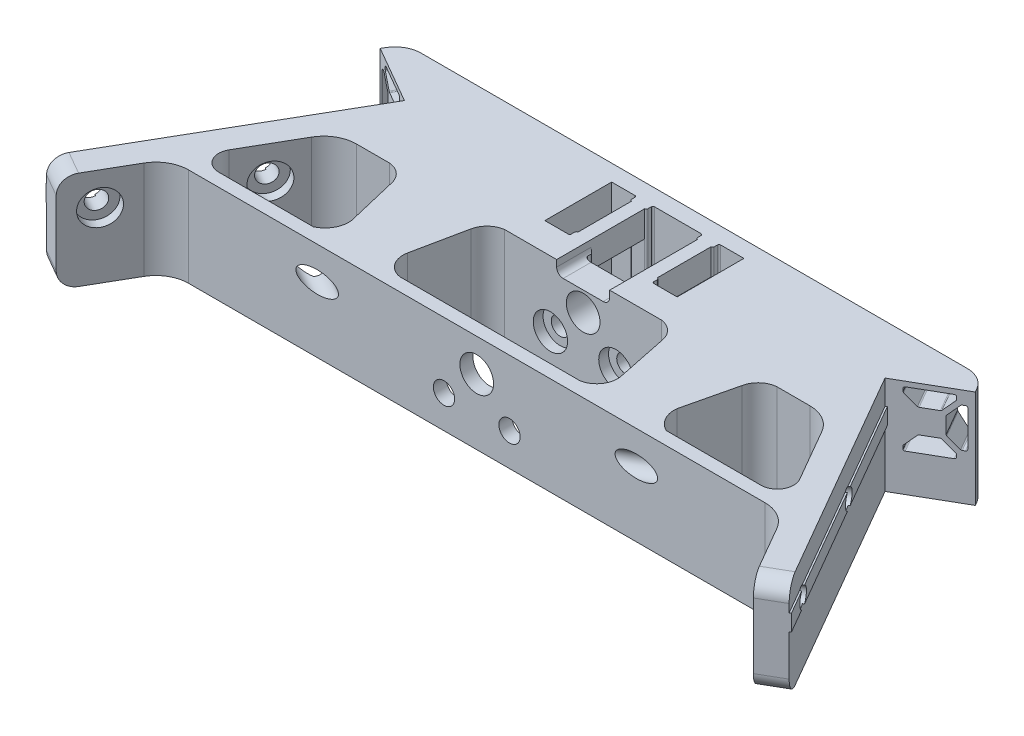
SolidWorks part; units mm, degrees
ref_plane "Front Plane" through (0, 0, 0) normal (0, 0, 1) x (1, 0, 0)
ref_plane "Top Plane" through (0, 0, 0) normal (0, 1, 0) x (1, 0, 0)
ref_plane "Right Plane" through (0, 0, 0) normal (1, 0, 0) x (0, 0, -1)
sketch "Sketch1" plane through (0, 0, 0) normal (0, 1, 0) x (1, 0, 0)
  line L0 (0, -61.4) -> (0, -111.1933) construction
  line L1 (0, 0) -> (-7.6, 0) construction
  line L2 (0, 0) -> (0, -20.4) construction
  line L3 (0, -20.4) -> (-7.1, -20.4) construction
  line L4 (-20.2, 0) -> (-20.2, -20.4)
  line L5 (0, 5) -> (-83.3812, 5)
  line L6 (-90.3094, 1) -> (-90.8868, 0)
  line L7 (-90.8868, 0) -> (-73.393, -10.1)
  line L8 (-73.393, -10.1) -> (-113.393, -79.382)
  line L9 (-113.393, -79.382) -> (-106.4648, -83.382)
  line L10 (-106.4648, -83.382) -> (-96.6603, -66.4)
  line L11 (-69.2361, -28.9) -> (0, -28.9)
  line L12 (0, -57.4) -> (0, -61.4)
  line L13 (0, -20.4) -> (-7.1, -20.4)
  line L14 (-20.2, 0) -> (-13.1, 0)
  line L16 (-82.8038, -57.4) -> (0, -57.4)
  line L17 (0, -20.4) -> (0, -28.9)
  line L18 (0, -61.4) -> (-88, -61.4)
  line L19 (-87.134, -49.9) -> (-77.8964, -33.9)
  line L20 (0, 0) -> (0, -20.4) construction
  line L21 (-7.6, -0.5) -> (-7.6, -1.5)
  line L22 (-20.2, -10.2) -> (0, -10.2) construction
  line L23 (-8.1, -2) -> (-12.1, -2)
  line L24 (-12.6, -0.5) -> (-12.6, -1.5)
  line L25 (-12.6, -19.9) -> (-12.6, -18.9)
  line L26 (-8.1, -18.4) -> (-12.1, -18.4)
  line L28 (-7.1, 0) -> (0, 0)
  line L29 (-7.6, -19.9) -> (-7.6, -18.9)
  line L30 (-13.1, -20.4) -> (-20.2, -20.4) construction
  line L31 (-13.1, -20.4) -> (-20.2, -20.4)
  line L32 (0, -28.9) -> (0, -57.4) construction
  line L33 (0, 5) -> (0, 0)
  arc A0 (-88, -61.4) -> (-96.6603, -66.4) centre (-88, -71.4) ccw
  arc A1 (-77.8964, -33.9) -> (-69.2361, -28.9) centre (-69.2361, -38.9) cw
  arc A2 (-82.8038, -57.4) -> (-87.134, -49.9) centre (-82.8038, -52.4) cw
  arc A3 (-83.3812, 5) -> (-90.3094, 1) centre (-83.3812, -3) ccw
  arc A4 (-7.1, 0) -> (-7.6, -0.5) centre (-7.1, -0.5) ccw
  arc A5 (-12.6, -0.5) -> (-13.1, 0) centre (-13.1, -0.5) ccw
  arc A6 (-7.6, -1.5) -> (-8.1, -2) centre (-8.1, -1.5) cw
  arc A7 (-12.1, -2) -> (-12.6, -1.5) centre (-12.1, -1.5) cw
  arc A10 (-12.1, -18.4) -> (-12.6, -18.9) centre (-12.1, -18.9) ccw
  arc A11 (-7.6, -18.9) -> (-8.1, -18.4) centre (-8.1, -18.9) ccw
  arc A12 (-12.6, -19.9) -> (-13.1, -20.4) centre (-13.1, -19.9) cw
  arc A13 (-7.1, -20.4) -> (-7.6, -19.9) centre (-7.1, -19.9) cw
  point P24 (-91.4641, -57.4)
  point P27 (-88, 5)
  point P30 (-10.1, 0)
  point P63 (-10.1, -20.4)
  dimension "D13" = 10
  dimension "D14" = 5
  dimension "D15" = 8
  dimension "D17" = 0.5
  dimension "D18" = 20.2
  dimension "D2" = 20.4
  dimension "D3" = 5
  dimension "D4" = 88
  dimension "D5" = 120
  dimension "D6" = 5
  dimension "D7" = 20.2
  dimension "D8" = 80
  dimension "D9" = 8
  dimension "D10" = 8.5
  dimension "D11" = 4
  dimension "D12" = 37
  dimension "D16" = 5
extrude "Boss-Extrude2" add sketch "Sketch1" along normal blind 30
sketch "Sketch2" plane through (-50.6714, 0, -29.2551) normal (-0.866, 0, -0.5) x (-0.5, 0, 0.866)
  line L0 (45.4434, 30) -> (45.4434, 0) construction
  line L1 (45.4434, 22.5) -> (125.4434, 22.5)
  line L2 (45.4434, 22.5) -> (45.4434, 17.5)
  line L3 (45.4434, 17.5) -> (125.4434, 17.5)
  line L4 (125.4434, 22.5) -> (125.4434, 17.5)
  line L5 (125.4434, 30) -> (125.4434, 0) construction
  line L7 (45.4434, 15) -> (125.4434, 15) construction
  line L9 (45.4434, 30) -> (125.4434, 30) construction
  dimension "D1" = 5
  dimension "D2" = 7.5
extrude "Boss-Extrude3" add sketch "Sketch2" along normal blind 0.5
hole_wizard "CBORE for M5 SHCS2" positions "Sketch5" profile "Sketch4" counterbore size "M5" standard "ANSI Metric" end condition up to next
sketch "Sketch5" plane through (-43.7431, 0, -25.2551) normal (0.866, 0, 0.5) x (0.5, 0, -0.866)
  line L0 (-125.4434, 20) -> (-68.3064, 20) construction
  line L1 (-125.4434, 30) -> (-125.4434, 0) construction
  line L2 (-68.3064, 30) -> (-68.3064, 0) construction
  line L4 (-86.7817, 30) -> (-68.3064, 30) construction
  line L10 (-125.4434, 30) -> (-105.8342, 30) construction
  line L11 (-115.6388, 30) -> (-115.6388, 20) construction
  line L13 (-77.5441, 30) -> (-77.5441, 20) construction
  point P0 (-77.5441, 20)
  point P4 (-115.6388, 20)
  dimension "D1" = 10
sketch "Sketch4" plane through (-82.5152, 20, 41.9) normal (0, 1, 0) x (0.5, 0, -0.866)
  line L0 (0, 0) -> (0, 8.5)
  line L1 (0, 8.5) -> (2.75, 8.5)
  line L3 (2.75, 8.5) -> (2.75, 3)
  line L4 (2.75, 3) -> (5.25, 3)
  line L5 (5.25, 3) -> (5.25, 0)
  line L7 (5.25, 0) -> (0, 0)
  line L11 (0, -6.35) -> (0, 107.95) construction
  dimension "Thru Hole Dia." = 5.5
  dimension "Thru Hole Depth" = 8.5
  dimension "C'Bore Dia." = 10.5
  dimension "C'Bore Depth" = 3
hole_wizard "CBORE for M5 SHCS3" positions "Sketch7" profile "Sketch6" counterbore size "M5" standard "ANSI Metric" end condition up to next
sketch "Sketch7" plane through (0, 0, 28.9) normal (0, 0, 1) x (1, 0, 0)
  line L0 (0, 60) -> (0, 0) construction
  line L2 (-69.2361, 0) -> (0, 0) construction
  line L4 (0, 10) -> (-28.3411, 10)
  line L10 (0, 30) -> (0, 0) construction
  line L11 (-69.2361, 0) -> (0, 0) construction
  point P2 (-10, 10)
  dimension "D1" = 10
  dimension "D2" = 10
sketch "Sketch6" plane through (-10, 10, 28.9) normal (1, 0, 0) x (0, -1, 0)
  line L0 (0, 0) -> (0, 10.5)
  line L1 (0, 10.5) -> (2.75, 10.5)
  line L3 (2.75, 10.5) -> (2.75, 3)
  line L4 (2.75, 3) -> (5.25, 3)
  line L5 (5.25, 3) -> (5.25, 0)
  line L7 (5.25, 0) -> (0, 0)
  line L11 (0, -6.35) -> (0, 107.95) construction
  dimension "Thru Hole Dia." = 5.5
  dimension "Thru Hole Depth" = 10.5
  dimension "C'Bore Dia." = 10.5
  dimension "C'Bore Depth" = 3
fillet "Fillet1" radius 5 2 edges at (-109.9289, 0, 81.382) (-109.9289, 30, 81.382)
sketch "Sketch17" plane through (0, 0, 0) normal (0, 1, 0) x (1, 0, 0)
  line L0 (-77.8964, -33.9) -> (-8.392, -33.9) construction
  line L1 (0, -57.4) -> (-82.8038, -57.4) construction
  line L2 (-87.134, -49.9) -> (-8.392, -49.9) construction
  line L3 (-49.7313, -49.9) -> (-53.5337, -33.9)
  line L4 (-69.2361, -28.9) -> (0, -28.9) construction
  line L5 (-29.3026, -33.9) -> (-32.6088, -49.9)
  line L6 (-59.1642, -28.9) -> (-23.9792, -28.9)
  line L7 (-69.2361, -28.9) -> (0, -28.9) construction
  line L8 (-27.5009, -57.4) -> (-53.9252, -57.4)
  arc A0 (-29.3026, -33.9) -> (-23.9792, -28.9) centre (-23.0863, -35.1845) cw
  arc A1 (-32.6088, -49.9) -> (-27.5009, -57.4) centre (-26.4248, -51.1778) ccw
  arc A2 (-53.5337, -33.9) -> (-59.1642, -28.9) centre (-59.7018, -35.1756) ccw
  arc A3 (-49.7313, -49.9) -> (-53.9252, -57.4) centre (-56.9594, -50.7807) cw
  point P22 (-53.9252, -57.4)
  point P25 (-60.4891, -28.9)
  point P26 (-60.4891, -28.9)
  point P29 (-25.9078, -57.4)
  point P32 (-22.3891, -28.9)
extrude "Boss-Extrude5" add sketch "Sketch17" along normal up to surface (30 mm away) up to face at (-35.0167, 30, 22.2446)
sketch "Sketch21" plane through (-22.7217, 0, 39.3551) normal (-0.5, 0, 0.866) x (0.866, 0, 0.5)
  line L0 (-70.8942, 16.345) -> (-66.1263, 16.345)
  line L1 (-65.7671, 16.1962) -> (-62.664, 13.0931)
  line L2 (-62.5152, 12.7339) -> (-62.5152, 12.008)
  line L3 (-63.0232, 11.5) -> (-73.9972, 11.5)
  line L4 (-70.8147, 17.8751) -> (-70.6351, 17.6955)
  line L5 (-66.3853, 17.6955) -> (-66.2057, 17.8751)
  line L6 (-66.2057, 22.1249) -> (-66.3853, 22.3045)
  line L7 (-70.6351, 22.3045) -> (-70.8147, 22.1249)
  line L8 (-70.8147, 17.8751) -> (-70.6351, 17.6955) construction
  line L9 (-66.3853, 17.6955) -> (-66.2057, 17.8751) construction
  line L10 (-66.2057, 22.1249) -> (-66.3853, 22.3045) construction
  line L11 (-70.6351, 22.3045) -> (-70.8147, 22.1249) construction
  line L12 (-74.5052, 12.008) -> (-74.5052, 12.7339)
  line L13 (-74.3564, 13.0931) -> (-71.2534, 16.1962)
  line L14 (-72.1652, 22.3839) -> (-72.1652, 17.6161)
  line L15 (-72.314, 17.2569) -> (-75.4171, 14.1538)
  line L16 (-75.7763, 14.005) -> (-76.5022, 14.005)
  line L17 (-77.0102, 14.513) -> (-77.0102, 25.487)
  line L18 (-76.5022, 25.995) -> (-75.7763, 25.995)
  line L19 (-75.4171, 25.8462) -> (-72.314, 22.7431)
  line L20 (-73.9972, 28.5) -> (-63.0232, 28.5)
  line L21 (-62.5152, 27.992) -> (-62.5152, 27.2661)
  line L22 (-62.664, 26.9069) -> (-65.7671, 23.8038)
  line L23 (-66.1263, 23.655) -> (-70.8942, 23.655)
  line L24 (-71.2534, 23.8038) -> (-74.3564, 26.9069)
  line L25 (-74.5052, 27.2661) -> (-74.5052, 27.992)
  line L52 (-74.5052, 12.008) -> (-74.5052, 12.7339)
  line L53 (-71.6482, 11.5) -> (-73.9972, 11.5)
  line L54 (-71.1402, 10.508) -> (-71.1402, 10.992)
  line L55 (-77.0102, 10) -> (-71.6482, 10)
  line L56 (-78.5102, 16.862) -> (-78.5102, 11.5)
  line L57 (-77.5182, 17.37) -> (-78.0022, 17.37)
  line L58 (-77.0102, 14.513) -> (-77.0102, 16.862)
  line L59 (-75.7763, 14.005) -> (-76.5022, 14.005)
  line L60 (-72.314, 17.2569) -> (-75.4171, 14.1538)
  line L61 (-72.1652, 22.3839) -> (-72.1652, 17.6161)
  line L62 (-75.4171, 25.8462) -> (-72.314, 22.7431)
  line L63 (-76.5022, 25.995) -> (-75.7763, 25.995)
  line L64 (-77.0102, 23.138) -> (-77.0102, 25.487)
  line L65 (-78.0022, 22.63) -> (-77.5182, 22.63)
  line L66 (-78.5102, 28.5) -> (-78.5102, 23.138)
  line L67 (-71.6482, 30) -> (-77.0102, 30)
  line L68 (-71.1402, 29.008) -> (-71.1402, 29.492)
  line L69 (-73.9972, 28.5) -> (-71.6482, 28.5)
  line L70 (-74.5052, 27.2661) -> (-74.5052, 27.992)
  line L71 (-71.2534, 23.8038) -> (-74.3564, 26.9069)
  line L72 (-66.1263, 23.655) -> (-70.8942, 23.655)
  line L73 (-62.664, 26.9069) -> (-65.7671, 23.8038)
  line L74 (-62.5152, 27.992) -> (-62.5152, 27.2661)
  line L75 (-65.3722, 28.5) -> (-63.0232, 28.5)
  line L76 (-65.8802, 29.492) -> (-65.8802, 29.008)
  line L77 (-60.0102, 30) -> (-65.3722, 30)
  line L78 (-58.5102, 23.138) -> (-58.5102, 28.5)
  line L79 (-59.5022, 22.63) -> (-59.0182, 22.63)
  line L80 (-60.0102, 25.487) -> (-60.0102, 23.138)
  line L81 (-61.2442, 25.995) -> (-60.5182, 25.995)
  line L82 (-64.7064, 22.7431) -> (-61.6034, 25.8462)
  line L83 (-64.8552, 17.6161) -> (-64.8552, 22.3839)
  line L84 (-61.6034, 14.1538) -> (-64.7064, 17.2569)
  line L85 (-60.5182, 14.005) -> (-61.2442, 14.005)
  line L86 (-60.0102, 16.862) -> (-60.0102, 14.513)
  line L87 (-59.0182, 17.37) -> (-59.5022, 17.37)
  line L88 (-58.5102, 11.5) -> (-58.5102, 16.862)
  line L89 (-65.3722, 10) -> (-60.0102, 10)
  line L90 (-65.8802, 10.992) -> (-65.8802, 10.508)
  line L91 (-63.0232, 11.5) -> (-65.3722, 11.5)
  line L92 (-62.5152, 12.7339) -> (-62.5152, 12.008)
  line L93 (-65.7671, 16.1962) -> (-62.664, 13.0931)
  line L94 (-70.8942, 16.345) -> (-66.1263, 16.345)
  line L95 (-74.3564, 13.0931) -> (-71.2534, 16.1962)
  line L96 (-74.5052, 12.008) -> (-74.5052, 12.7339) construction
  line L97 (-71.6482, 11.5) -> (-73.9972, 11.5) construction
  line L98 (-71.1402, 10.508) -> (-71.1402, 10.992) construction
  line L99 (-77.0102, 10) -> (-71.6482, 10) construction
  line L100 (-78.5102, 16.862) -> (-78.5102, 11.5) construction
  line L101 (-77.5182, 17.37) -> (-78.0022, 17.37) construction
  line L102 (-77.0102, 14.513) -> (-77.0102, 16.862) construction
  line L103 (-75.7763, 14.005) -> (-76.5022, 14.005) construction
  line L104 (-72.314, 17.2569) -> (-75.4171, 14.1538) construction
  line L105 (-72.1652, 22.3839) -> (-72.1652, 17.6161) construction
  line L106 (-75.4171, 25.8462) -> (-72.314, 22.7431) construction
  line L107 (-76.5022, 25.995) -> (-75.7763, 25.995) construction
  line L108 (-77.0102, 23.138) -> (-77.0102, 25.487) construction
  line L109 (-78.0022, 22.63) -> (-77.5182, 22.63) construction
  line L110 (-78.5102, 28.5) -> (-78.5102, 23.138) construction
  line L111 (-71.6482, 30) -> (-77.0102, 30) construction
  line L112 (-71.1402, 29.008) -> (-71.1402, 29.492) construction
  line L113 (-73.9972, 28.5) -> (-71.6482, 28.5) construction
  line L114 (-74.5052, 27.2661) -> (-74.5052, 27.992) construction
  line L115 (-71.2534, 23.8038) -> (-74.3564, 26.9069) construction
  line L116 (-66.1263, 23.655) -> (-70.8942, 23.655) construction
  line L117 (-62.664, 26.9069) -> (-65.7671, 23.8038) construction
  line L118 (-62.5152, 27.992) -> (-62.5152, 27.2661) construction
  line L119 (-65.3722, 28.5) -> (-63.0232, 28.5) construction
  line L120 (-65.8802, 29.492) -> (-65.8802, 29.008) construction
  line L121 (-60.0102, 30) -> (-65.3722, 30) construction
  line L122 (-58.5102, 23.138) -> (-58.5102, 28.5) construction
  line L123 (-59.5022, 22.63) -> (-59.0182, 22.63) construction
  line L124 (-60.0102, 25.487) -> (-60.0102, 23.138) construction
  line L125 (-61.2442, 25.995) -> (-60.5182, 25.995) construction
  line L126 (-64.7064, 22.7431) -> (-61.6034, 25.8462) construction
  line L127 (-64.8552, 17.6161) -> (-64.8552, 22.3839) construction
  line L128 (-61.6034, 14.1538) -> (-64.7064, 17.2569) construction
  line L129 (-60.5182, 14.005) -> (-61.2442, 14.005) construction
  line L130 (-60.0102, 16.862) -> (-60.0102, 14.513) construction
  line L131 (-59.0182, 17.37) -> (-59.5022, 17.37) construction
  line L132 (-58.5102, 11.5) -> (-58.5102, 16.862) construction
  line L133 (-65.3722, 10) -> (-60.0102, 10) construction
  line L134 (-65.8802, 10.992) -> (-65.8802, 10.508) construction
  line L135 (-63.0232, 11.5) -> (-65.3722, 11.5) construction
  line L136 (-62.5152, 12.7339) -> (-62.5152, 12.008) construction
  line L137 (-65.7671, 16.1962) -> (-62.664, 13.0931) construction
  line L138 (-70.8942, 16.345) -> (-66.1263, 16.345) construction
  line L139 (-74.3564, 13.0931) -> (-71.2534, 16.1962) construction
  arc A0 (-66.1263, 16.345) -> (-65.7671, 16.1962) centre (-66.1263, 15.837) cw
  arc A1 (-62.664, 13.0931) -> (-62.5152, 12.7339) centre (-63.0232, 12.7339) cw
  arc A2 (-62.5152, 12.008) -> (-63.0232, 11.5) centre (-63.0232, 12.008) cw
  arc A3 (-73.9972, 11.5) -> (-74.5052, 12.008) centre (-73.9972, 12.008) cw
  arc A4 (-74.5052, 12.7339) -> (-74.3564, 13.0931) centre (-73.9972, 12.7339) cw
  arc A5 (-71.2534, 16.1962) -> (-70.8942, 16.345) centre (-70.8942, 15.837) cw
  arc A6 (-72.1652, 17.6161) -> (-72.314, 17.2569) centre (-72.6732, 17.6161) cw
  arc A7 (-75.4171, 14.1538) -> (-75.7763, 14.005) centre (-75.7763, 14.513) cw
  arc A8 (-76.5022, 14.005) -> (-77.0102, 14.513) centre (-76.5022, 14.513) cw
  arc A9 (-77.0102, 25.487) -> (-76.5022, 25.995) centre (-76.5022, 25.487) cw
  arc A10 (-75.7763, 25.995) -> (-75.4171, 25.8462) centre (-75.7763, 25.487) cw
  arc A11 (-72.314, 22.7431) -> (-72.1652, 22.3839) centre (-72.6732, 22.3839) cw
  arc A12 (-70.6351, 17.6955) -> (-69.3142, 18.0649) centre (-70.0786, 18.252) ccw
  arc A13 (-69.3142, 18.0649) -> (-67.7063, 18.0649) centre (-68.5102, 20) ccw
  arc A14 (-67.7063, 18.0649) -> (-66.3853, 17.6955) centre (-66.9418, 18.252) ccw
  arc A15 (-66.2057, 17.8751) -> (-66.5751, 19.196) centre (-66.7622, 18.4316) ccw
  arc A16 (-66.5751, 19.196) -> (-66.5751, 20.804) centre (-68.5102, 20) ccw
  arc A17 (-66.5751, 20.804) -> (-66.2057, 22.1249) centre (-66.7622, 21.5684) ccw
  arc A18 (-66.3853, 22.3045) -> (-67.7063, 21.9351) centre (-66.9418, 21.748) ccw
  arc A19 (-67.7063, 21.9351) -> (-69.3142, 21.9351) centre (-68.5102, 20) ccw
  arc A20 (-69.3142, 21.9351) -> (-70.6351, 22.3045) centre (-70.0786, 21.748) ccw
  arc A21 (-70.8147, 22.1249) -> (-70.4454, 20.804) centre (-70.2582, 21.5684) ccw
  arc A22 (-70.4454, 20.804) -> (-70.4454, 19.196) centre (-68.5102, 20) ccw
  arc A23 (-70.4454, 19.196) -> (-70.8147, 17.8751) centre (-70.2582, 18.4316) ccw
  arc A24 (-70.6351, 17.6955) -> (-69.3142, 18.0649) centre (-70.0786, 18.252) ccw construction
  arc A25 (-69.3142, 18.0649) -> (-67.7063, 18.0649) centre (-68.5102, 20) ccw construction
  arc A26 (-67.7063, 18.0649) -> (-66.3853, 17.6955) centre (-66.9418, 18.252) ccw construction
  arc A27 (-66.2057, 17.8751) -> (-66.5751, 19.196) centre (-66.7622, 18.4316) ccw construction
  arc A28 (-66.5751, 19.196) -> (-66.5751, 20.804) centre (-68.5102, 20) ccw construction
  arc A29 (-66.5751, 20.804) -> (-66.2057, 22.1249) centre (-66.7622, 21.5684) ccw construction
  arc A30 (-66.3853, 22.3045) -> (-67.7063, 21.9351) centre (-66.9418, 21.748) ccw construction
  arc A31 (-67.7063, 21.9351) -> (-69.3142, 21.9351) centre (-68.5102, 20) ccw construction
  arc A32 (-69.3142, 21.9351) -> (-70.6351, 22.3045) centre (-70.0786, 21.748) ccw construction
  arc A33 (-70.8147, 22.1249) -> (-70.4454, 20.804) centre (-70.2582, 21.5684) ccw construction
  arc A34 (-70.4454, 20.804) -> (-70.4454, 19.196) centre (-68.5102, 20) ccw construction
  arc A35 (-70.4454, 19.196) -> (-70.8147, 17.8751) centre (-70.2582, 18.4316) ccw construction
  arc A36 (-63.0232, 28.5) -> (-62.5152, 27.992) centre (-63.0232, 27.992) cw
  arc A37 (-62.5152, 27.2661) -> (-62.664, 26.9069) centre (-63.0232, 27.2661) cw
  arc A38 (-65.7671, 23.8038) -> (-66.1263, 23.655) centre (-66.1263, 24.163) cw
  arc A39 (-70.8942, 23.655) -> (-71.2534, 23.8038) centre (-70.8942, 24.163) cw
  arc A40 (-74.3564, 26.9069) -> (-74.5052, 27.2661) centre (-73.9972, 27.2661) cw
  arc A41 (-74.5052, 27.992) -> (-73.9972, 28.5) centre (-73.9972, 27.992) cw
  arc A68 (-74.5052, 12.008) -> (-73.9972, 11.5) centre (-73.9972, 12.008) ccw
  arc A69 (-71.1402, 10.992) -> (-71.6482, 11.5) centre (-71.6482, 10.992) ccw
  arc A70 (-71.6482, 10) -> (-71.1402, 10.508) centre (-71.6482, 10.508) ccw
  arc A71 (-78.5102, 11.5) -> (-77.0102, 10) centre (-77.0102, 11.5) ccw
  arc A72 (-78.0022, 17.37) -> (-78.5102, 16.862) centre (-78.0022, 16.862) ccw
  arc A73 (-77.0102, 16.862) -> (-77.5182, 17.37) centre (-77.5182, 16.862) ccw
  arc A74 (-77.0102, 14.513) -> (-76.5022, 14.005) centre (-76.5022, 14.513) ccw
  arc A75 (-75.7763, 14.005) -> (-75.4171, 14.1538) centre (-75.7763, 14.513) ccw
  arc A76 (-72.314, 17.2569) -> (-72.1652, 17.6161) centre (-72.6732, 17.6161) ccw
  arc A77 (-72.1652, 22.3839) -> (-72.314, 22.7431) centre (-72.6732, 22.3839) ccw
  arc A78 (-75.4171, 25.8462) -> (-75.7763, 25.995) centre (-75.7763, 25.487) ccw
  arc A79 (-76.5022, 25.995) -> (-77.0102, 25.487) centre (-76.5022, 25.487) ccw
  arc A80 (-77.5182, 22.63) -> (-77.0102, 23.138) centre (-77.5182, 23.138) ccw
  arc A81 (-78.5102, 23.138) -> (-78.0022, 22.63) centre (-78.0022, 23.138) ccw
  arc A82 (-77.0102, 30) -> (-78.5102, 28.5) centre (-77.0102, 28.5) ccw
  arc A83 (-71.1402, 29.492) -> (-71.6482, 30) centre (-71.6482, 29.492) ccw
  arc A84 (-71.6482, 28.5) -> (-71.1402, 29.008) centre (-71.6482, 29.008) ccw
  arc A85 (-73.9972, 28.5) -> (-74.5052, 27.992) centre (-73.9972, 27.992) ccw
  arc A86 (-74.5052, 27.2661) -> (-74.3564, 26.9069) centre (-73.9972, 27.2661) ccw
  arc A87 (-71.2534, 23.8038) -> (-70.8942, 23.655) centre (-70.8942, 24.163) ccw
  arc A88 (-66.1263, 23.655) -> (-65.7671, 23.8038) centre (-66.1263, 24.163) ccw
  arc A89 (-62.664, 26.9069) -> (-62.5152, 27.2661) centre (-63.0232, 27.2661) ccw
  arc A90 (-62.5152, 27.992) -> (-63.0232, 28.5) centre (-63.0232, 27.992) ccw
  arc A91 (-65.8802, 29.008) -> (-65.3722, 28.5) centre (-65.3722, 29.008) ccw
  arc A92 (-65.3722, 30) -> (-65.8802, 29.492) centre (-65.3722, 29.492) ccw
  arc A93 (-58.5102, 28.5) -> (-60.0102, 30) centre (-60.0102, 28.5) ccw
  arc A94 (-59.0182, 22.63) -> (-58.5102, 23.138) centre (-59.0182, 23.138) ccw
  arc A95 (-60.0102, 23.138) -> (-59.5022, 22.63) centre (-59.5022, 23.138) ccw
  arc A96 (-60.0102, 25.487) -> (-60.5182, 25.995) centre (-60.5182, 25.487) ccw
  arc A97 (-61.2442, 25.995) -> (-61.6034, 25.8462) centre (-61.2442, 25.487) ccw
  arc A98 (-64.7064, 22.7431) -> (-64.8552, 22.3839) centre (-64.3472, 22.3839) ccw
  arc A99 (-64.8552, 17.6161) -> (-64.7064, 17.2569) centre (-64.3472, 17.6161) ccw
  arc A100 (-61.6034, 14.1538) -> (-61.2442, 14.005) centre (-61.2442, 14.513) ccw
  arc A101 (-60.5182, 14.005) -> (-60.0102, 14.513) centre (-60.5182, 14.513) ccw
  arc A102 (-59.5022, 17.37) -> (-60.0102, 16.862) centre (-59.5022, 16.862) ccw
  arc A103 (-58.5102, 16.862) -> (-59.0182, 17.37) centre (-59.0182, 16.862) ccw
  arc A104 (-60.0102, 10) -> (-58.5102, 11.5) centre (-60.0102, 11.5) ccw
  arc A105 (-65.8802, 10.508) -> (-65.3722, 10) centre (-65.3722, 10.508) ccw
  arc A106 (-65.3722, 11.5) -> (-65.8802, 10.992) centre (-65.3722, 10.992) ccw
  arc A107 (-63.0232, 11.5) -> (-62.5152, 12.008) centre (-63.0232, 12.008) ccw
  arc A108 (-62.5152, 12.7339) -> (-62.664, 13.0931) centre (-63.0232, 12.7339) ccw
  arc A109 (-65.7671, 16.1962) -> (-66.1263, 16.345) centre (-66.1263, 15.837) ccw
  arc A110 (-70.8942, 16.345) -> (-71.2534, 16.1962) centre (-70.8942, 15.837) ccw
  arc A111 (-74.3564, 13.0931) -> (-74.5052, 12.7339) centre (-73.9972, 12.7339) ccw
  arc A112 (-74.5052, 12.008) -> (-73.9972, 11.5) centre (-73.9972, 12.008) ccw construction
  arc A113 (-71.1402, 10.992) -> (-71.6482, 11.5) centre (-71.6482, 10.992) ccw construction
  arc A114 (-71.6482, 10) -> (-71.1402, 10.508) centre (-71.6482, 10.508) ccw construction
  arc A115 (-78.5102, 11.5) -> (-77.0102, 10) centre (-77.0102, 11.5) ccw construction
  arc A116 (-78.0022, 17.37) -> (-78.5102, 16.862) centre (-78.0022, 16.862) ccw construction
  arc A117 (-77.0102, 16.862) -> (-77.5182, 17.37) centre (-77.5182, 16.862) ccw construction
  arc A118 (-77.0102, 14.513) -> (-76.5022, 14.005) centre (-76.5022, 14.513) ccw construction
  arc A119 (-75.7763, 14.005) -> (-75.4171, 14.1538) centre (-75.7763, 14.513) ccw construction
  arc A120 (-72.314, 17.2569) -> (-72.1652, 17.6161) centre (-72.6732, 17.6161) ccw construction
  arc A121 (-72.1652, 22.3839) -> (-72.314, 22.7431) centre (-72.6732, 22.3839) ccw construction
  arc A122 (-75.4171, 25.8462) -> (-75.7763, 25.995) centre (-75.7763, 25.487) ccw construction
  arc A123 (-76.5022, 25.995) -> (-77.0102, 25.487) centre (-76.5022, 25.487) ccw construction
  arc A124 (-77.5182, 22.63) -> (-77.0102, 23.138) centre (-77.5182, 23.138) ccw construction
  arc A125 (-78.5102, 23.138) -> (-78.0022, 22.63) centre (-78.0022, 23.138) ccw construction
  arc A126 (-77.0102, 30) -> (-78.5102, 28.5) centre (-77.0102, 28.5) ccw construction
  arc A127 (-71.1402, 29.492) -> (-71.6482, 30) centre (-71.6482, 29.492) ccw construction
  arc A128 (-71.6482, 28.5) -> (-71.1402, 29.008) centre (-71.6482, 29.008) ccw construction
  arc A129 (-73.9972, 28.5) -> (-74.5052, 27.992) centre (-73.9972, 27.992) ccw construction
  arc A130 (-74.5052, 27.2661) -> (-74.3564, 26.9069) centre (-73.9972, 27.2661) ccw construction
  arc A131 (-71.2534, 23.8038) -> (-70.8942, 23.655) centre (-70.8942, 24.163) ccw construction
  arc A132 (-66.1263, 23.655) -> (-65.7671, 23.8038) centre (-66.1263, 24.163) ccw construction
  arc A133 (-62.664, 26.9069) -> (-62.5152, 27.2661) centre (-63.0232, 27.2661) ccw construction
  arc A134 (-62.5152, 27.992) -> (-63.0232, 28.5) centre (-63.0232, 27.992) ccw construction
  arc A135 (-65.8802, 29.008) -> (-65.3722, 28.5) centre (-65.3722, 29.008) ccw construction
  arc A136 (-65.3722, 30) -> (-65.8802, 29.492) centre (-65.3722, 29.492) ccw construction
  arc A137 (-58.5102, 28.5) -> (-60.0102, 30) centre (-60.0102, 28.5) ccw construction
  arc A138 (-59.0182, 22.63) -> (-58.5102, 23.138) centre (-59.0182, 23.138) ccw construction
  arc A139 (-60.0102, 23.138) -> (-59.5022, 22.63) centre (-59.5022, 23.138) ccw construction
  arc A140 (-60.0102, 25.487) -> (-60.5182, 25.995) centre (-60.5182, 25.487) ccw construction
  arc A141 (-61.2442, 25.995) -> (-61.6034, 25.8462) centre (-61.2442, 25.487) ccw construction
  arc A142 (-64.7064, 22.7431) -> (-64.8552, 22.3839) centre (-64.3472, 22.3839) ccw construction
  arc A143 (-64.8552, 17.6161) -> (-64.7064, 17.2569) centre (-64.3472, 17.6161) ccw construction
  arc A144 (-61.6034, 14.1538) -> (-61.2442, 14.005) centre (-61.2442, 14.513) ccw construction
  arc A145 (-60.5182, 14.005) -> (-60.0102, 14.513) centre (-60.5182, 14.513) ccw construction
  arc A146 (-59.5022, 17.37) -> (-60.0102, 16.862) centre (-59.5022, 16.862) ccw construction
  arc A147 (-58.5102, 16.862) -> (-59.0182, 17.37) centre (-59.0182, 16.862) ccw construction
  arc A148 (-60.0102, 10) -> (-58.5102, 11.5) centre (-60.0102, 11.5) ccw construction
  arc A149 (-65.8802, 10.508) -> (-65.3722, 10) centre (-65.3722, 10.508) ccw construction
  arc A150 (-65.3722, 11.5) -> (-65.8802, 10.992) centre (-65.3722, 10.992) ccw construction
  arc A151 (-63.0232, 11.5) -> (-62.5152, 12.008) centre (-63.0232, 12.008) ccw construction
  arc A152 (-62.5152, 12.7339) -> (-62.664, 13.0931) centre (-63.0232, 12.7339) ccw construction
  arc A153 (-65.7671, 16.1962) -> (-66.1263, 16.345) centre (-66.1263, 15.837) ccw construction
  arc A154 (-70.8942, 16.345) -> (-71.2534, 16.1962) centre (-70.8942, 15.837) ccw construction
  arc A155 (-74.3564, 13.0931) -> (-74.5052, 12.7339) centre (-73.9972, 12.7339) ccw construction
  dimension "D1" = 0
  dimension "D2" = 0
sketch "Sketch22" plane through (-22.7217, 0, 39.3551) normal (-0.5, 0, 0.866) x (0.866, 0, 0.5)
  line L6 (-77.0102, 25.487) -> (-77.0102, 14.513)
  line L7 (-76.5022, 14.005) -> (-75.7763, 14.005)
  line L8 (-75.4171, 14.1538) -> (-72.314, 17.2569)
  line L9 (-72.1652, 17.6161) -> (-72.1652, 22.3839)
  line L10 (-72.314, 22.7431) -> (-75.4171, 25.8462)
  line L11 (-75.7763, 25.995) -> (-76.5022, 25.995)
  line L12 (-77.0102, 25.487) -> (-77.0102, 14.513)
  line L13 (-76.5022, 14.005) -> (-75.7763, 14.005)
  line L14 (-75.4171, 14.1538) -> (-72.314, 17.2569)
  line L15 (-72.1652, 17.6161) -> (-72.1652, 22.3839)
  line L16 (-72.314, 22.7431) -> (-75.4171, 25.8462)
  line L17 (-75.7763, 25.995) -> (-76.5022, 25.995)
  line L18 (-63.0232, 28.5) -> (-73.9972, 28.5)
  line L19 (-74.5052, 27.992) -> (-74.5052, 27.2661)
  line L20 (-74.3564, 26.9069) -> (-71.2534, 23.8038)
  line L21 (-70.8942, 23.655) -> (-66.1263, 23.655)
  line L22 (-65.7671, 23.8038) -> (-62.664, 26.9069)
  line L23 (-62.5152, 27.2661) -> (-62.5152, 27.992)
  line L24 (-63.0232, 28.5) -> (-73.9972, 28.5)
  line L25 (-74.5052, 27.992) -> (-74.5052, 27.2661)
  line L26 (-74.3564, 26.9069) -> (-71.2534, 23.8038)
  line L27 (-70.8942, 23.655) -> (-66.1263, 23.655)
  line L28 (-65.7671, 23.8038) -> (-62.664, 26.9069)
  line L29 (-62.5152, 27.2661) -> (-62.5152, 27.992)
  line L30 (-66.1263, 16.345) -> (-70.8942, 16.345)
  line L31 (-62.664, 13.0931) -> (-65.7671, 16.1962)
  line L32 (-62.5152, 12.008) -> (-62.5152, 12.7339)
  line L33 (-73.9972, 11.5) -> (-63.0232, 11.5)
  line L34 (-74.5052, 12.7339) -> (-74.5052, 12.008)
  line L35 (-71.2534, 16.1962) -> (-74.3564, 13.0931)
  line L36 (-66.1263, 16.345) -> (-70.8942, 16.345)
  line L37 (-62.664, 13.0931) -> (-65.7671, 16.1962)
  line L38 (-62.5152, 12.008) -> (-62.5152, 12.7339)
  line L39 (-73.9972, 11.5) -> (-63.0232, 11.5)
  line L40 (-74.5052, 12.7339) -> (-74.5052, 12.008)
  line L41 (-71.2534, 16.1962) -> (-74.3564, 13.0931)
  arc A6 (-77.0102, 14.513) -> (-76.5022, 14.005) centre (-76.5022, 14.513) ccw
  arc A7 (-75.7763, 14.005) -> (-75.4171, 14.1538) centre (-75.7763, 14.513) ccw
  arc A8 (-72.314, 17.2569) -> (-72.1652, 17.6161) centre (-72.6732, 17.6161) ccw
  arc A9 (-72.1652, 22.3839) -> (-72.314, 22.7431) centre (-72.6732, 22.3839) ccw
  arc A10 (-75.4171, 25.8462) -> (-75.7763, 25.995) centre (-75.7763, 25.487) ccw
  arc A11 (-76.5022, 25.995) -> (-77.0102, 25.487) centre (-76.5022, 25.487) ccw
  arc A12 (-77.0102, 14.513) -> (-76.5022, 14.005) centre (-76.5022, 14.513) ccw
  arc A13 (-75.7763, 14.005) -> (-75.4171, 14.1538) centre (-75.7763, 14.513) ccw
  arc A14 (-72.314, 17.2569) -> (-72.1652, 17.6161) centre (-72.6732, 17.6161) ccw
  arc A15 (-72.1652, 22.3839) -> (-72.314, 22.7431) centre (-72.6732, 22.3839) ccw
  arc A16 (-75.4171, 25.8462) -> (-75.7763, 25.995) centre (-75.7763, 25.487) ccw
  arc A17 (-76.5022, 25.995) -> (-77.0102, 25.487) centre (-76.5022, 25.487) ccw
  arc A18 (-73.9972, 28.5) -> (-74.5052, 27.992) centre (-73.9972, 27.992) ccw
  arc A19 (-74.5052, 27.2661) -> (-74.3564, 26.9069) centre (-73.9972, 27.2661) ccw
  arc A20 (-71.2534, 23.8038) -> (-70.8942, 23.655) centre (-70.8942, 24.163) ccw
  arc A21 (-66.1263, 23.655) -> (-65.7671, 23.8038) centre (-66.1263, 24.163) ccw
  arc A22 (-62.664, 26.9069) -> (-62.5152, 27.2661) centre (-63.0232, 27.2661) ccw
  arc A23 (-62.5152, 27.992) -> (-63.0232, 28.5) centre (-63.0232, 27.992) ccw
  arc A24 (-73.9972, 28.5) -> (-74.5052, 27.992) centre (-73.9972, 27.992) ccw
  arc A25 (-74.5052, 27.2661) -> (-74.3564, 26.9069) centre (-73.9972, 27.2661) ccw
  arc A26 (-71.2534, 23.8038) -> (-70.8942, 23.655) centre (-70.8942, 24.163) ccw
  arc A27 (-66.1263, 23.655) -> (-65.7671, 23.8038) centre (-66.1263, 24.163) ccw
  arc A28 (-62.664, 26.9069) -> (-62.5152, 27.2661) centre (-63.0232, 27.2661) ccw
  arc A29 (-62.5152, 27.992) -> (-63.0232, 28.5) centre (-63.0232, 27.992) ccw
  arc A30 (-65.7671, 16.1962) -> (-66.1263, 16.345) centre (-66.1263, 15.837) ccw
  arc A31 (-62.5152, 12.7339) -> (-62.664, 13.0931) centre (-63.0232, 12.7339) ccw
  arc A32 (-63.0232, 11.5) -> (-62.5152, 12.008) centre (-63.0232, 12.008) ccw
  arc A33 (-74.5052, 12.008) -> (-73.9972, 11.5) centre (-73.9972, 12.008) ccw
  arc A34 (-74.3564, 13.0931) -> (-74.5052, 12.7339) centre (-73.9972, 12.7339) ccw
  arc A35 (-70.8942, 16.345) -> (-71.2534, 16.1962) centre (-70.8942, 15.837) ccw
  arc A36 (-65.7671, 16.1962) -> (-66.1263, 16.345) centre (-66.1263, 15.837) ccw
  arc A37 (-62.5152, 12.7339) -> (-62.664, 13.0931) centre (-63.0232, 12.7339) ccw
  arc A38 (-63.0232, 11.5) -> (-62.5152, 12.008) centre (-63.0232, 12.008) ccw
  arc A39 (-74.5052, 12.008) -> (-73.9972, 11.5) centre (-73.9972, 12.008) ccw
  arc A40 (-74.3564, 13.0931) -> (-74.5052, 12.7339) centre (-73.9972, 12.7339) ccw
  arc A41 (-70.8942, 16.345) -> (-71.2534, 16.1962) centre (-70.8942, 15.837) ccw
  dimension "D1" = 0
  dimension "D2" = 0
  dimension "D3" = 0
extrude "Cut-Extrude9" cut sketch "Sketch22" against normal up to next
sketch "Sketch23" plane through (-43.7431, 0, -25.2551) normal (0.866, 0, 0.5) x (0.5, 0, -0.866)
  circle A0 centre (-77.5441, 20) radius 3.25
  dimension "D1" = 6.5
extrude "Cut-Extrude10" cut sketch "Sketch23" along normal up to surface (44.6292 mm away) up to face at (-44, 15, 61.4)
sketch "Sketch24" plane through (0, 0, 28.9) normal (0, 0, 1) x (1, 0, 0)
  circle A0 centre (-10, 10) radius 3.25
  dimension "D1" = 6.5
extrude "Cut-Extrude11" cut sketch "Sketch24" along normal up to surface (32.5 mm away) up to face at (-44, 15, 61.4)
mirror "Mirror1" about plane through (0, 30, 20.4) normal (-1, 0, 0) of bodies 121 102
sketch "Sketch12" plane through (0, 0, 2) normal (0, 0, 1) x (1, 0, 0)
  line L1 (-8.1, 30) -> (-8.1, 0) construction
  line L2 (-12.1, 30) -> (-8.1, 30)
  line L3 (-12.1, 30) -> (-12.1, 22)
  line L4 (-12.1, 22) -> (-8.1, 22)
  line L5 (0, 0) -> (0, 31.3528) construction
  line L6 (-8.1, 30) -> (-8.1, 22)
  line L7 (8.1, 30) -> (8.1, 22)
  line L8 (12.1, 22) -> (8.1, 22)
  line L9 (12.1, 30) -> (12.1, 22)
  line L11 (12.1, 30) -> (8.1, 30)
  dimension "D1" = 8
extrude "Boss-Extrude4" add sketch "Sketch12" along normal up to next
sketch "Sketch13" plane through (0, 0, 28.9) normal (0, 0, 1) x (1, 0, 0)
  line L2 (-8.1, 30) -> (8.1, 30)
  line L3 (-8.1, 30) -> (-8.1, 28)
  line L4 (-6.1, 26) -> (6.1, 26)
  line L6 (8.1, 30) -> (8.1, 28)
  arc A0 (6.1, 26) -> (8.1, 28) centre (6.1, 28) ccw
  arc A1 (-8.1, 28) -> (-6.1, 26) centre (-6.1, 28) ccw
  dimension "D1" = 16.2
  dimension "D3" = 2
  dimension "D2" = 4
extrude "Cut-Extrude4" cut sketch "Sketch13" against normal up to next
sketch "Sketch18" plane through (0, 0, 28.9) normal (0, 0, 1) x (1, 0, 0)
  line L0 (-23.9792, 20) -> (23.9792, 20) construction
  line L1 (-23.9792, 30) -> (-23.9792, 0) construction
  line L2 (23.9792, 30) -> (23.9792, 0) construction
  line L3 (-23.9792, 30) -> (-8.1, 30) construction
  circle A0 centre (0, 20) radius 5.15
  dimension "D1" = 10.3
  dimension "D2" = 10
extrude "Cut-Extrude5" cut sketch "Sketch18" against normal up to surface (8.5 mm away) up to face at (0, 17.4007, 20.4)
sketch "Sketch20" plane through (0, 0, 61.4) normal (0, 0, 1) x (1, 0, 0)
  circle A1 centre (0, 20) radius 5.15
  circle A2 centre (0, 20) radius 5.15
  dimension "D1" = 0
extrude "Cut-Extrude7" cut sketch "Sketch20" against normal up to next
